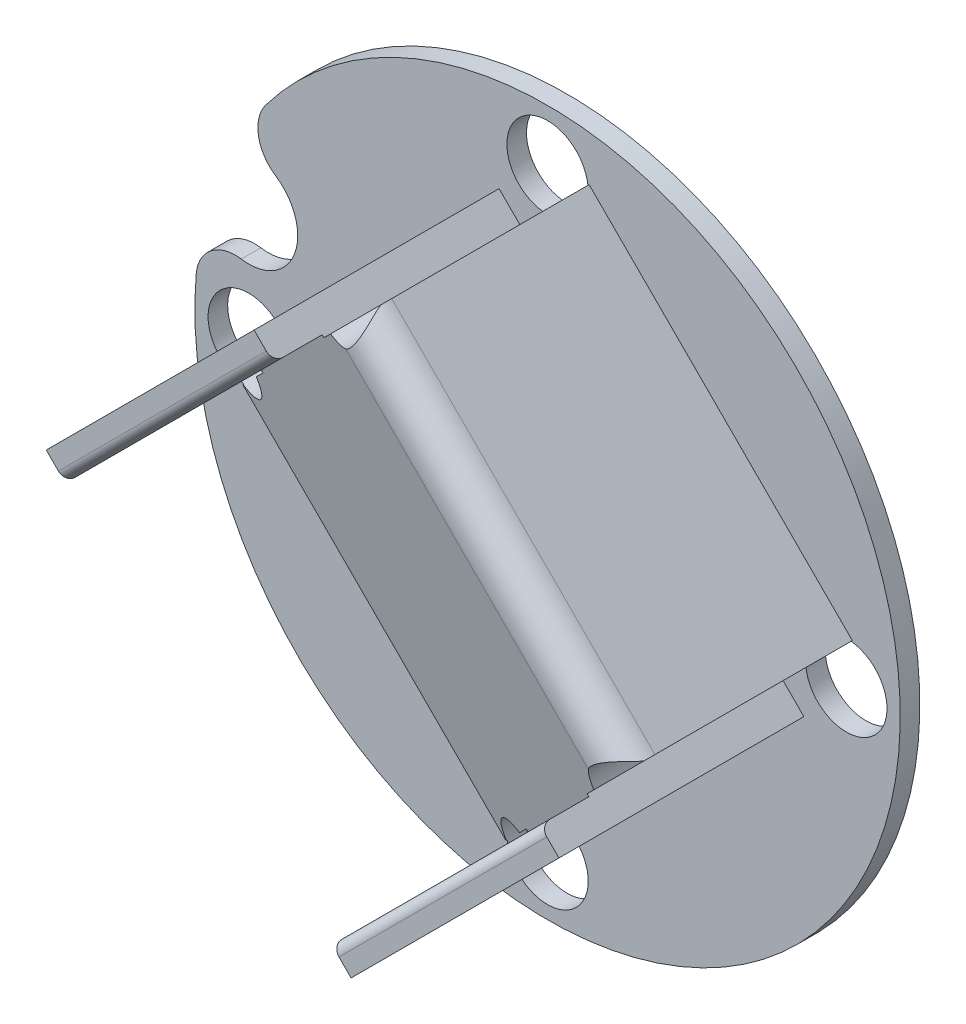
SolidWorks part; units mm, degrees
ref_plane "前视基准面" through (0, 0, 0) normal (0, 0, 1) x (1, 0, 0)
ref_plane "上视基准面" through (0, 0, 0) normal (0, 1, 0) x (1, 0, 0)
ref_plane "右视基准面" through (0, 0, 0) normal (1, 0, 0) x (0, 0, -1)
sketch "草图1" plane through (0, 0, 0) normal (0, 0, 1) x (1, 0, 0)
  circle A0 centre (0, 0) radius 30.5
  circle A1 centre (0, 30.5) radius 4.15
  circle A2 centre (-30.5, 0) radius 4.15
  circle A3 centre (0, -30.5) radius 4.15
  circle A4 centre (30.5, 0) radius 4.15
  circle A5 centre (0, 0) radius 36
extrude "凸台-拉伸1" add sketch "草图1" along normal blind 2 contours A5 A4 A0 A3 A2 A1 | A4 A0 A1 A2 A3 region at (0, 0, 0) region at (-34.9818, 0, 0)
sketch "草图2" plane through (0, 0, 2) normal (0, 0, 1) x (1, 0, 0)
  line L1 (-22.5, -22.5) -> (22.5, -22.5)
  line L2 (-22.5, -22.5) -> (-22.5, 22.5)
  line L3 (-22.5, 22.5) -> (22.5, 22.5)
  line L4 (22.5, -22.5) -> (22.5, 22.5)
  line L5 (-22.5, -22.5) -> (22.5, 22.5) construction
  line L6 (-22.5, 22.5) -> (22.5, -22.5) construction
  point P0 (0, 0)
  dimension "D1" = 45
  dimension "D2" = 45
extrude "凸台-拉伸2" add sketch "草图2" along normal blind 25
sketch "草图3" plane through (0, 0, 27) normal (0, 0, 1) x (1, 0, 0)
  circle A0 centre (0, 0) radius 36
  circle A1 centre (0, 30.5) radius 4.15
  circle A2 centre (0, -30.5) radius 4.15
  circle A3 centre (-30.5, 0) radius 4.15
  circle A4 centre (30.5, 0) radius 4.15
extrude "凸台-拉伸3" add sketch "草图3" along normal blind 2 contours A0 | A3 | A4 | A2 | A1
sketch "草图8" plane through (0, 0, 29) normal (0, 0, 1) x (1, 0, 0)
  line L0 (0, 0) -> (-25.4558, 25.4558)
  line L1 (0, 0) -> (25.4558, 25.4558)
  line L2 (-25.4558, 25.4558) -> (25.4558, -25.4558)
  line L3 (0, 0) -> (-25.4558, -25.4558)
  line L4 (0, 0) -> (17.6777, 17.6777)
  line L5 (0, 0) -> (-17.6777, 17.6777)
  line L6 (0, 0) -> (-17.6777, -17.6777)
  line L7 (0, 0) -> (17.6777, -17.6777)
  line L8 (17.6777, 17.6777) -> (31.1127, 4.2426)
  line L9 (17.6777, 17.6777) -> (4.2426, 31.1127)
  line L10 (-31.1127, -4.2426) -> (4.2426, 31.1127)
  line L11 (31.1127, 4.2426) -> (-4.2426, -31.1127)
  line L14 (-17.6777, -17.6777) -> (-31.1127, -4.2426)
  line L15 (-31.1127, -4.2426) -> (-4.2426, -31.1127)
  circle A0 centre (0, 0) radius 36 construction
  circle M6 centre (0, -30.5) radius 4.15
  circle M7 centre (-30.5, 0) radius 4.15
  circle M9 centre (30.5, 0) radius 4.15
  circle M10 centre (0, 30.5) radius 4.15
extrude "凸台-拉伸4" add sketch "草图8" along normal blind 25 contours L10 L0 L1 L9 M10 | L11 L8 L1 L2 M9 | L14 L3 L0 L10 M7 | L3 L15 L11 L2 M6 region at (-15.3613, -2.119, 29) region at (2.119, 15.3613, 29) region at (15.3613, 2.119, 29) region at (-2.119, -15.3613, 29)
sketch "草图12" plane through (13.435, -13.435, 0) normal (0.7071, -0.7071, 0) x (0, 0, -1)
  line L0 (-54, 25) -> (-29, -25)
  line L2 (-54, -25) -> (-29, -25)
  line L3 (-54, -25) -> (-54, 25)
  line L5 (-29, -25) -> (-29, 25)
  line M5 (-29, 18.3057) -> (-54, 18.3057)
  line M6 (-54, 18.3057) -> (-54, -18.3057)
  line M7 (-54, -18.3057) -> (-29, -18.3057)
extrude "切除-拉伸1" cut sketch "草图12" against normal blind 50 contours L0 M5 M6 M7 | L3 L0 M5 | L3 L2 L0 M7 region at (27.957, 1.0869, 52.8843) region at (10.2757, -16.5944, 46.633) region at (-1.9325, -28.8025, 42.3168)
sketch "草图13" plane through (0, 0, 29) normal (0, 0, 1) x (1, 0, 0)
  line L0 (-17.6777, -17.6777) -> (-28.2843, -7.0711)
  line L1 (-4.2426, -31.1127) -> (-31.1127, -4.2426) construction
  line L2 (-28.2843, -7.0711) -> (-7.0711, -28.2843)
  line L3 (-7.0711, -28.2843) -> (-9.1924, -30.4056)
  line L4 (-9.1924, -30.4056) -> (-30.4056, -9.1924)
  line L5 (-30.4056, -9.1924) -> (-28.2843, -7.0711)
sketch "草图16" plane through (0, 0, 29) normal (0, 0, 1) x (1, 0, 0)
  line L0 (-13.435, 13.435) -> (-2.8284, 24.0416)
  line L1 (-26.3791, 0.4909) -> (-0.4909, 26.3791) construction
  line L2 (-13.435, 13.435) -> (-24.0416, 2.8284)
  line L3 (-26.3791, 0.4909) -> (-0.4909, 26.3791) construction
  line L4 (-24.0416, 2.8284) -> (-26.163, 4.9497)
  line L5 (-26.163, 4.9497) -> (-4.9497, 26.163)
  line L6 (-4.9497, 26.163) -> (-2.8284, 24.0416)
  line L7 (13.435, -13.435) -> (24.0416, -2.8284)
  line L8 (26.3791, -0.4909) -> (0.4909, -26.3791) construction
  line L9 (26.3791, -0.4909) -> (0.4909, -26.3791) construction
  line L10 (24.0416, -2.8284) -> (26.163, -4.9497)
  line L11 (26.163, -4.9497) -> (4.9497, -26.163)
  line L12 (4.9497, -26.163) -> (2.8284, -24.0416)
  line L13 (2.8284, -24.0416) -> (24.0416, -2.8284)
  line M6 (-26.3791, 0.4909) -> (-0.4909, 26.3791)
  line M12 (26.3791, -0.4909) -> (0.4909, -26.3791)
extrude "凸台-拉伸6" add sketch "草图16" along normal blind 25 contours L6 L5 L4 M6 | L12 L11 L10 M12 region at (-14.4957, 14.4957, 29) region at (14.4957, -14.4957, 29)
sketch "草图17" plane through (-13.435, 13.435, 0) normal (0.7071, -0.7071, 0) x (0, 0, -1)
  line L0 (-49, 15) -> (-34, -15)
  line L1 (-34, -15) -> (-54, -15)
  line L2 (-54, -15) -> (-54, 15)
  line L3 (-54, 15) -> (-49, 15)
extrude "切除-拉伸3" cut sketch "草图17" against normal blind 0.25 and the other way blind 38.25
sketch "草图18" plane through (-13.6118, 13.6118, 0) normal (0.7071, -0.7071, 0) x (0, 0, -1)
  line L0 (-49, 15) -> (-34, -15)
  line L1 (-34, -15) -> (-29, -12.5)
  line L2 (-29, 15) -> (-29, -15) construction
  line L3 (-41.5, 0) -> (-36.5, 2.5)
  line L4 (-36.5, 2.5) -> (-42.3138, 14.1276)
  line L5 (-36.5, 2.5) -> (-30.6862, -9.1276)
  line L6 (-30.6862, -9.1276) -> (-29, -8.2844)
  line L7 (-30.6862, -9.1276) -> (-32.5735, -10.0712)
  line L8 (-42.3138, 14.1276) -> (-44.201, 13.1839)
  line L9 (-44.201, 13.1839) -> (-32.5735, -10.0712)
  line L10 (-29, -8.2844) -> (-40.831, 14.869)
  line L11 (-40.831, 14.869) -> (-42.3138, 14.1276)
extrude "切除-拉伸4" cut sketch "草图18" against normal blind 4 and the other way blind 50 contours L8 L9 L3 L4 | L3 L9 L7 L5 | L10 L11 L4 L5 L6 region at (-8.0667, 19.1569, 40.3505) region at (-16.2886, 10.935, 34.5367) region at (-11.7395, 15.4841, 35.5823)
sketch "草图20" plane through (0, 0, 0) normal (0, 0, -1) x (-1, 0, 0)
  line L1 (-22.5, -22.5) -> (22.5, -22.5)
  line L2 (-22.5, -22.5) -> (-22.5, 22.5)
  line L3 (-22.5, 22.5) -> (22.5, 22.5)
  line L4 (22.5, -22.5) -> (22.5, 22.5)
  line L5 (-22.5, -22.5) -> (22.5, 22.5) construction
  line L6 (-22.5, 22.5) -> (22.5, -22.5) construction
  point P0 (0, 0)
  dimension "D1" = 45
  dimension "D2" = 45
extrude "凸台-拉伸7" add sketch "草图20" along normal blind 13 contours L2 L1 L4 L3
sketch "草图21" plane through (0, 0, 0) normal (0, 0, -1) x (-1, 0, 0)
  circle A0 centre (27.868, 11.6757) radius 4.2
fillet "圆角1" radius 3 1 edges at (17.6777, 17.6777, 54)
fillet "圆角2" radius 1 2 edges at (13.6118, -13.6118, 54) (-13.6118, 13.6118, 54)
sketch "草图22" plane through (0, 0, -13) normal (0, 0, -1) x (-1, 0, 0)
  circle A0 centre (0, 0) radius 36
extrude "切除-拉伸6" cut sketch "草图22" against normal blind 40
sketch "草图23" plane through (0, 0, 27) normal (0, 0, -1) x (-1, 0, 0)
  line L0 (30.5, 0) -> (-30.5, 0)
  line L1 (30.5, 0) -> (30.5, 11.72)
sketch "草图24" plane through (0, 0, 27) normal (0, 0, -1) x (-1, 0, 0)
  circle A0 centre (30.5, 11.72) radius 5
extrude "切除-拉伸7" cut sketch "草图24" against normal blind 2
fillet "圆角3" radius 4 2 edges at (-34.8089, 9.1836, 28) (-32.0017, 16.4892, 28)
